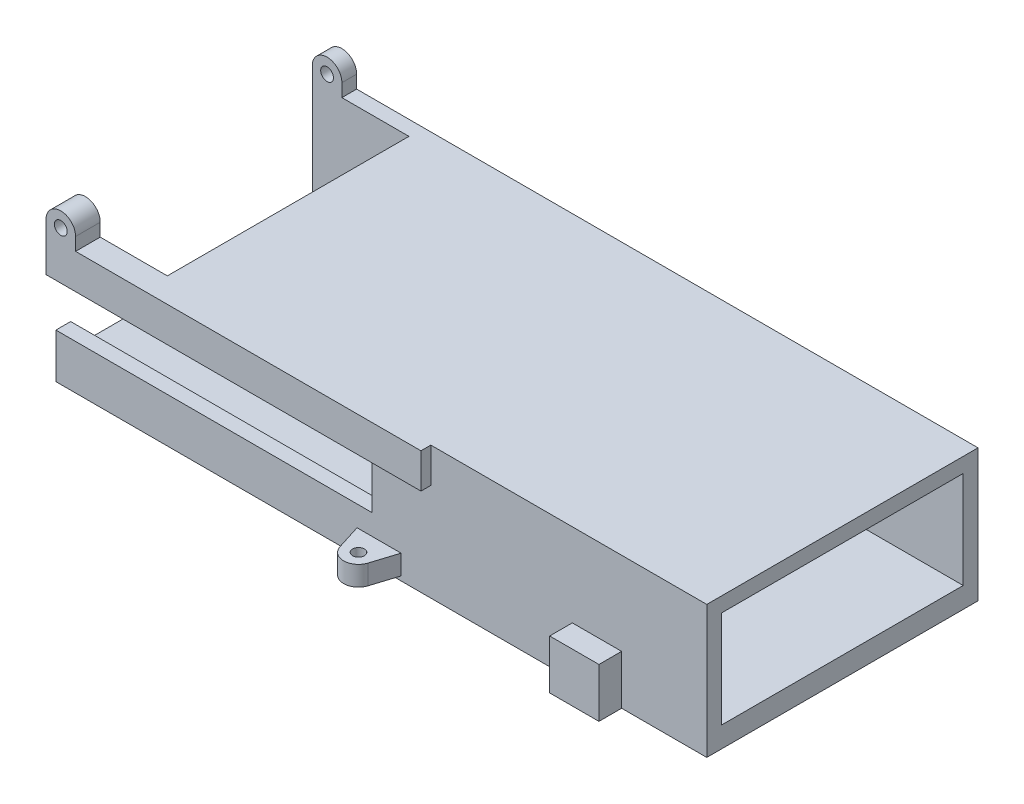
SolidWorks part; units mm, degrees
ref_plane "前视基准面" through (0, 0, 0) normal (0, 0, 1) x (1, 0, 0)
ref_plane "上视基准面" through (0, 0, 0) normal (0, 1, 0) x (1, 0, 0)
ref_plane "右视基准面" through (0, 0, 0) normal (1, 0, 0) x (0, 0, -1)
other "Configuration Table"
sketch "草图1" plane through (0, 0, 0) normal (1, 0, 0) x (0, 0, -1)
  line L0 (-13.75, 5.45) -> (-13.75, -5.45)
  line L1 (-12.25, 3.95) -> (12.25, 3.95)
  line L2 (-12.25, 3.95) -> (-12.25, -3.95)
  line L3 (-12.25, -3.95) -> (12.25, -3.95)
  line L4 (12.25, 3.95) -> (12.25, -3.95)
  line L5 (-12.25, 3.95) -> (12.25, -3.95) construction
  line L6 (-12.25, -3.95) -> (12.25, 3.95) construction
  line L7 (-13.75, -5.45) -> (13.75, -5.45)
  line L8 (13.75, 5.45) -> (13.75, -5.45)
  line L9 (-13.75, 5.45) -> (13.75, 5.45)
  point P0 (0, 0)
  dimension "D1" = 7.9
  dimension "D2" = 24.5
  dimension "D3" = 1.5
extrude "凸台-拉伸1" add sketch "草图1" along normal blind 66
sketch "草图3" plane through (0, 0, 13.75) normal (0, 0, 1) x (1, 0, 0)
  line L5 (-3.2135, 0) -> (138.373, 0)
  line L6 (-3.2135, 0) -> (-3.2135, -11.0772)
  line L7 (-3.2135, -11.0772) -> (138.373, -11.0772)
  line L8 (138.373, 0) -> (138.373, -11.0772)
extrude "切除-拉伸1" cut sketch "草图3" against normal blind 50
sketch "草图4" plane through (0, 0, 13.75) normal (0, 0, 1) x (1, 0, 0)
  line L0 (0, 6.7589) -> (0, 5.45)
  line L1 (0, 5.45) -> (0, 0) construction
  line L2 (3, 6.7589) -> (3, 5.45)
  line L3 (0, 5.45) -> (3, 5.45)
  line L4 (66, 5.45) -> (0, 5.45) construction
  circle A0 centre (1.5, 6.7589) radius 0.65
  arc A1 (3, 6.7589) -> (0, 6.7589) centre (1.5, 6.7589) ccw
  dimension "D1" = 1.3
  dimension "D2" = 3
extrude "凸台-拉伸2" add sketch "草图4" against normal up to surface (27.5 mm away) up to face at (33, 2.725, -13.75)
sketch "草图5" plane through (0, 5.45, 0) normal (0, 1, 0) x (1, 0, 0)
  line L1 (-18.1453, 12.25) -> (9.8025, 12.25)
  line L2 (-18.1453, 12.25) -> (-18.1453, -12.25)
  line L3 (-18.1453, -12.25) -> (9.8025, -12.25)
  line L4 (9.8025, 12.25) -> (9.8025, -12.25)
  line L5 (-18.1453, 12.25) -> (9.8025, -12.25) construction
  line L6 (-18.1453, -12.25) -> (9.8025, 12.25) construction
  line L10 (66, 12.25) -> (0, 12.25) construction
  point P0 (-4.1714, 0)
extrude "切除-拉伸2" cut sketch "草图5" against normal blind 10 and the other way blind 10
sketch "草图6" plane through (66, 0, 0) normal (1, 0, 0) x (0, 0, -1)
  line L0 (-12.25, 3.95) -> (-12.25, 0) construction
  line L2 (-12.25, 0) -> (-12.25, -6.49)
  line L3 (-12.25, -6.49) -> (12.25, -6.49)
  line L4 (12.25, 0) -> (12.25, -6.49)
  line L5 (12.25, 0) -> (12.25, 3.95) construction
  line L6 (13.75, 0) -> (13.75, 5.45) construction
  line L7 (-13.75, 0) -> (-12.25, 0)
  line L8 (-13.75, 0) -> (-13.75, -7.99)
  line L9 (-13.75, -7.99) -> (13.75, -7.99)
  line L10 (13.75, 0) -> (13.75, -7.99)
  line L11 (-13.75, 5.45) -> (-13.75, 0) construction
  line L12 (12.25, 3.95) -> (-12.25, 3.95) construction
  line L13 (12.25, 0) -> (13.75, 0)
  dimension "D1" = 10.44
  dimension "D2" = 1.5
extrude "凸台-拉伸3" add sketch "草图6" against normal up to surface (66 mm away) up to face at (0, 3.3795, 13)
sketch "草图9" plane through (0, 5.45, 0) normal (0, 1, 0) x (1, 0, 0)
  line L0 (30.5373, -13.75) -> (31.3383, -16.2857)
  line L1 (66, -13.75) -> (3, -13.75) construction
  line L2 (34.199, -16.2857) -> (35, -13.75)
  line L3 (30.5373, -13.75) -> (35, -13.75)
  line L4 (0, -12.25) -> (0, -13.75) construction
  arc A0 (34.199, -16.2857) -> (31.3383, -16.2857) centre (32.7687, -15.8339) cw
  circle A1 centre (32.7687, -15.8339) radius 0.6
  dimension "D2" = 1.5
  dimension "D3" = 1.2
  dimension "D1" = 35
extrude "凸台-拉伸5" add sketch "草图9" against normal blind 2 from offset 11 offset against normal yes
sketch "草图10" plane through (0, 0, 13.75) normal (0, 0, 1) x (1, 0, 0)
  line L1 (-1.3843, 1.9083) -> (32.0584, 1.9083)
  line L2 (-1.3843, 1.9083) -> (-1.3843, -3.4602)
  line L3 (-1.3843, -3.4602) -> (32.0584, -3.4602)
  line L4 (32.0584, 1.9083) -> (32.0584, -3.4602)
extrude "切除-拉伸3" cut sketch "草图10" against normal blind 2.6
sketch "草图11" plane through (0, -7.99, 0) normal (0, -1, 0) x (1, 0, 0)
  line L0 (0, 13.75) -> (66, 13.75) construction
  line L1 (52.3661, 13.75) -> (57.3661, 13.75)
  line L2 (52.3661, 13.75) -> (52.3661, 16.05)
  line L3 (52.3661, 16.05) -> (57.3661, 16.05)
  line L4 (57.3661, 13.75) -> (57.3661, 16.05)
  line L5 (66, 13.75) -> (66, -13.75) construction
  dimension "D1" = 2.3
  dimension "D2" = 5
  dimension "D3" = 13.6339
extrude "凸台-拉伸6" add sketch "草图11" against normal blind 5
sketch "草图12" plane through (0, 0, 13.75) normal (0, 0, 1) x (1, 0, 0)
  line L0 (32.0584, 1.9083) -> (38.0191, 1.9083)
  line L1 (38.0191, 1.9083) -> (38.0191, 5.45)
  line L13 (0, -7.99) -> (52.3661, -7.99)
  line L14 (52.3661, -7.99) -> (52.3661, -2.99)
  line L15 (52.3661, -2.99) -> (57.3661, -2.99)
  line L16 (57.3661, -2.99) -> (57.3661, -7.99)
  line L17 (57.3661, -7.99) -> (66, -7.99)
  line L18 (66, -7.99) -> (66, 5.45)
  line L19 (66, 5.45) -> (3, 5.45)
  line L20 (3, 5.45) -> (3, 6.7589)
  line L21 (0, 6.7589) -> (0, 1.9083)
  line L22 (0, 1.9083) -> (32.0584, 1.9083)
  line L23 (32.0584, 1.9083) -> (32.0584, -3.4602)
  line L24 (32.0584, -3.4602) -> (0, -3.4602)
  line L25 (0, -3.4602) -> (0, -7.99)
  line L32 (38.0191, 5.45) -> (3, 5.45)
  line L33 (3, 5.45) -> (3, 6.7589)
  line L34 (0, 6.7589) -> (0, 1.9083)
  line L35 (0, 1.9083) -> (32.0584, 1.9083)
  circle A0 centre (1.5, 6.7589) radius 0.65 construction
  arc A1 (3, 6.7589) -> (0, 6.7589) centre (1.5, 6.7589) ccw
  arc A2 (3, 6.7589) -> (0, 6.7589) centre (1.5, 6.7589) ccw
  circle A3 centre (1.5, 6.7589) radius 0.65
  dimension "D1" = 0
extrude "凸台-拉伸7" add sketch "草图12" along normal blind 1
sketch "草图13" plane through (66, 0, 0) normal (1, 0, 0) x (0, 0, -1)
  line L0 (12.25, -6.49) -> (-12.25, -6.49) construction
  line L1 (-12.25, -6.49) -> (12.25, -6.49)
  line L2 (-12.25, -6.49) -> (-12.25, -5.89)
  line L3 (-12.25, -5.89) -> (12.25, -5.89)
  line L4 (12.25, -6.49) -> (12.25, -5.89)
  line L5 (-12.25, 3.95) -> (-12.25, -6.49) construction
  line L6 (12.25, -6.49) -> (12.25, 3.95) construction
  dimension "D1" = 0.6
extrude "凸台-拉伸8" add sketch "草图13" against normal up to surface (66 mm away) up to face at (0, -2.7953, 0)
